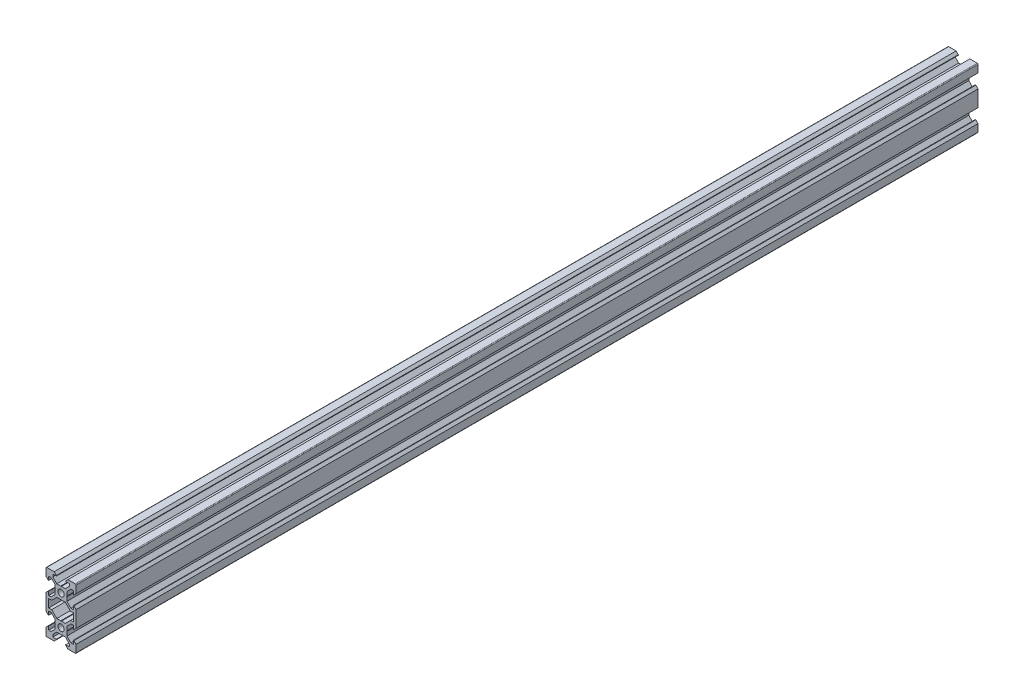
SolidWorks part; units mm, degrees
ref_plane "Plan de face" through (0, 0, 0) normal (0, 0, 1) x (1, 0, 0)
ref_plane "Plan de dessus" through (0, 0, 0) normal (0, 1, 0) x (1, 0, 0)
ref_plane "Plan de droite" through (0, 0, 0) normal (1, 0, 0) x (0, 0, -1)
ref_axis "Axe" through (0, 0, -13.782) along (0, 0, 1)
sketch "Esquisse1" plane through (0, 0, 0) normal (0, 0, 1) x (1, 0, 0)
  line L0 (0, 22.8977) -> (0, -22.8977) construction
  line L1 (-33.6074, 0) -> (33.6074, 0) construction
  line L2 (0, 0) -> (-22.2114, 22.2114) construction
  line L3 (-9.5, 10) -> (-4.58, 10)
  line L4 (-4.58, 10) -> (-3.125, 8.545)
  line L5 (-3.125, 8.545) -> (-3.125, 8.2)
  line L6 (-3.125, 8.2) -> (-5.5, 8.2)
  line L7 (-2.8393, 3.9) -> (-5.5, 6.5607)
  line L8 (-2.8393, 3.9) -> (-0.21, 3.9)
  line L9 (-5.5, 6.5607) -> (-5.5, 8.2)
  line L10 (0, 3.69) -> (0, 2.1)
  line L11 (-3.9, 2.8393) -> (-6.5607, 5.5)
  line L12 (-8.545, 3.125) -> (-8.2, 3.125)
  line L13 (-8.2, 3.125) -> (-8.2, 5.5)
  line L14 (-6.5607, 5.5) -> (-8.2, 5.5)
  line L15 (-10, 4.58) -> (-8.545, 3.125)
  line L16 (-10, 9.5) -> (-10, 4.58)
  line L17 (-0.21, 3.9) -> (0, 3.69)
  line L18 (-3.9, 2.8393) -> (-3.9, 0.21)
  line L20 (-3.9, 0.21) -> (-3.69, 0)
  line L21 (-0.21, -3.9) -> (0, -3.69)
  line L22 (0, -3.69) -> (0, -2.1)
  line L23 (-6.5607, -5.5) -> (-8.2, -5.5)
  line L24 (-2.8393, -3.9) -> (-0.21, -3.9)
  line L25 (-8.545, -3.125) -> (-8.2, -3.125)
  line L26 (-10, -4.58) -> (-8.545, -3.125)
  line L27 (-8.2, -3.125) -> (-8.2, -5.5)
  line L28 (-2.8393, -3.9) -> (-6.2393, -7.3)
  line L29 (-3.9, -2.8393) -> (-6.5607, -5.5)
  line L30 (-3.9, -2.8393) -> (-3.9, -0.21)
  line L31 (-3.9, -0.21) -> (-3.69, 0)
  line L32 (-6.2393, -7.3) -> (-8.2, -7.3)
  line L33 (-8.2, -7.3) -> (-8.2, -10)
  line L34 (-8.2, -10) -> (-10, -10)
  line L35 (-10, -10) -> (-10, -4.58)
  arc A0 (0, -2.1) -> (0, 2.1) centre (0, 0) cw
  arc A1 (-9.5, 10) -> (-10, 9.5) centre (-9.5, 9.5) ccw
  point P4 (0, 0)
  point P7 (0, 0)
  point P30 (-10, 10)
  dimension "D5" = 11
  dimension "D2" = 2.1
  dimension "D3" = 6.25
  dimension "D10" = 0.5
  dimension "D4" = 9.16
  dimension "D6" = 1.5
  dimension "D7" = 1.8
  dimension "D8" = 4.3
  dimension "D9" = 20
  dimension "D11" = 0.42
  dimension "D12" = 10
  dimension "D13" = 1.8
extrude "Boss.-Extru.1" add sketch "Esquisse1" along normal blind 600
sketch "Esquisse3" plane through (0, 0, 600) normal (0, 0, 1) x (1, 0, 0)
  line L0 (0, 0) -> (-9.8536, 9.8536) construction
  line L1 (-8.2, 8.2) -> (-8.2, 6.57)
  line L2 (-8.2, 6.57) -> (-7.54, 6.57)
  line L3 (-7.54, 6.57) -> (-6.57, 7.54)
  line L4 (-8.2, 3.125) -> (-8.2, 5.5) construction
  line L5 (-6.57, 8.2) -> (-6.57, 7.54)
  line L6 (-8.2, 8.2) -> (-6.57, 8.2)
  line L7 (-5.5, 6.5607) -> (-5.5, 8.2) construction
  arc A0 (-9.5, 10) -> (-10, 9.5) centre (-9.5, 9.5) ccw construction
  point P13 (-7.055, 7.055)
  point P14 (-6.57, 7.87)
  dimension "D1" = 1.07
extrude "Enlèv. mat.-Extru.1" [suppressed] cut sketch "Esquisse3" against normal through all
mirror "Symétrie1" about plane through (0, 3.69, 600) normal (-1, 0, 0) of "Enlèv. mat.-Extru.1", "Boss.-Extru.1"
mirror "Symétrie6" about plane through (-8.2, -10, 600) normal (0, 1, 0) of "Symétrie1", "Boss.-Extru.1"
